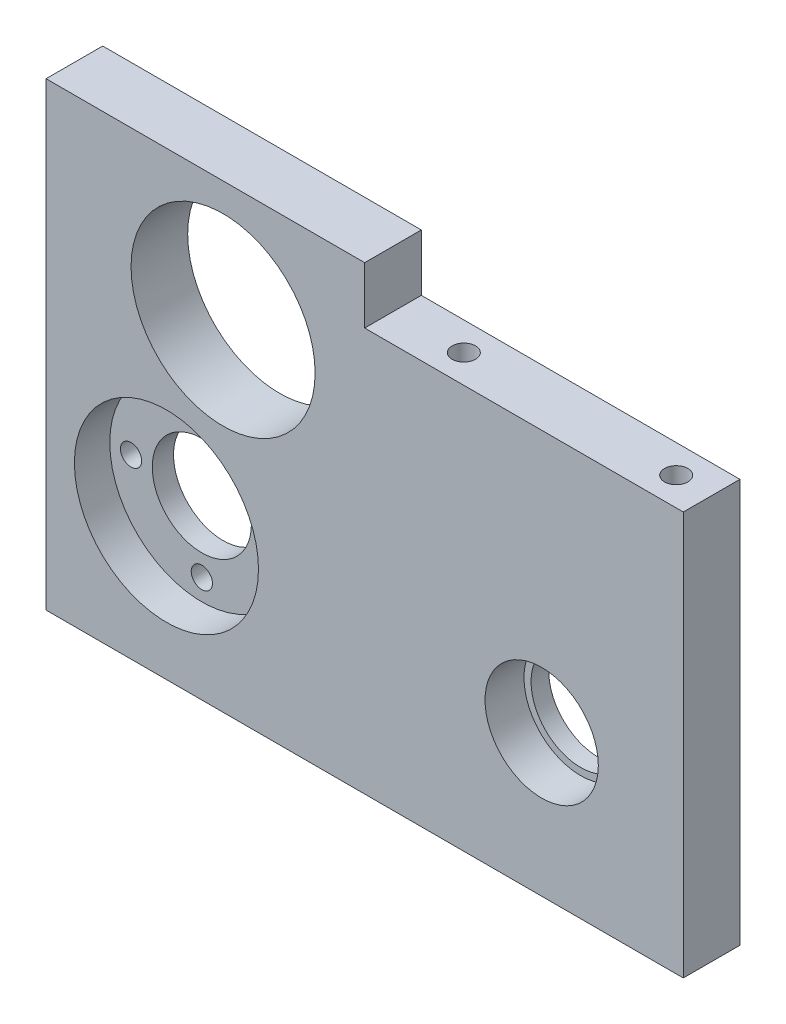
SolidWorks part; units mm, degrees
ref_plane "Front" through (0, 0, 0) normal (0, 0, 1) x (1, 0, 0)
ref_plane "Top" through (0, 0, 0) normal (0, 1, 0) x (1, 0, 0)
ref_plane "Right" through (0, 0, 0) normal (1, 0, 0) x (0, 0, -1)
sketch "Esquisse1" plane through (0, 0, 0) normal (0, 0, 1) x (1, 0, 0)
  line L1 (0, 0) -> (90, 0)
  line L2 (0, 0) -> (0, 65)
  line L3 (0, 65) -> (90, 65)
  line L4 (90, 0) -> (90, 65)
  circle A0 centre (70, 20) radius 7
  circle A1 centre (17, 20) radius 13
  circle A2 centre (25, 48) radius 13
  dimension "D3" = 14
  dimension "D4" = 20
  dimension "D6" = 53
  dimension "D8" = 26
  dimension "D9" = 26
  dimension "D1" = 90
  dimension "D2" = 65
  dimension "D5" = 70
  dimension "D7" = 20
  dimension "D10" = 53
  dimension "D11" = 48
extrude "Boss.-Extru.1" add sketch "Esquisse1" along normal blind 8
sketch "Esquisse2" plane through (0, 0, 0) normal (0, 0, -1) x (-1, 0, 0)
  circle A0 centre (-17, 20) radius 13
  circle A1 centre (-17, 20) radius 13 construction
extrude "Boss.-Extru.2" add sketch "Esquisse2" against normal blind 3
sketch "Esquisse3" plane through (0, 0, 3) normal (0, 0, 1) x (1, 0, 0)
  line L0 (27, 20) -> (17, 20) construction
  circle A0 centre (17, 20) radius 7
  circle A1 centre (27, 20) radius 1.5
  circle A2 centre (17, 10) radius 1.5
  circle A3 centre (7, 20) radius 1.5
  circle A4 centre (17, 30) radius 1.5
  point P13 (17, 20)
  dimension "D1" = 14
  dimension "D2" = 3
  dimension "D3" = 10
  dimension "D4" = 4
extrude "Enlèv. mat.-Extru.1" cut sketch "Esquisse3" against normal through all
sketch "Esquisse4" plane through (0, 0, 8) normal (0, 0, 1) x (1, 0, 0)
  circle A0 centre (70, 20) radius 8
  dimension "D1" = 16
extrude "Enlèv. mat.-Extru.2" cut sketch "Esquisse4" against normal blind 5.5
sketch "Esquisse5" plane through (0, 0, 8) normal (0, 0, 1) x (1, 0, 0)
  line L0 (90, 65) -> (0, 65) construction
  line L1 (45, 65) -> (90, 65)
  line L2 (45, 65) -> (45, 57)
  line L3 (45, 57) -> (90, 57)
  line L4 (90, 65) -> (90, 57)
  line L5 (90, 0) -> (90, 65) construction
  dimension "D1" = 8
  dimension "D2" = 45
extrude "Enlèv. mat.-Extru.3" cut sketch "Esquisse5" against normal through all
sketch "Esquisse6" plane through (0, 0, 0) normal (-1, 0, 0) x (0, 0, 1)
  line L0 (4, 0) -> (4, 65) construction
  line L1 (8, 0) -> (0, 0) construction
  line L2 (8, 65) -> (0, 65) construction
  circle A0 centre (4, 7) radius 1.65
  circle A1 centre (4, 35) radius 1.65
  dimension "D1" = 3.3
  dimension "D2" = 28
  dimension "D3" = 7
extrude "Enlèv. mat.-Extru.4" cut sketch "Esquisse6" against normal blind 10
sketch "Esquisse7" plane through (0, 57, 0) normal (0, 1, 0) x (1, 0, 0)
  line L0 (45, -4) -> (85, -4) construction
  line L1 (45, 0) -> (45, -8) construction
  circle A0 centre (85, -4) radius 1.65
  circle A1 centre (55, -4) radius 1.65
  dimension "D1" = 3.3
  dimension "D2" = 30
  dimension "D3" = 10
extrude "Enlèv. mat.-Extru.5" cut sketch "Esquisse7" against normal blind 10
